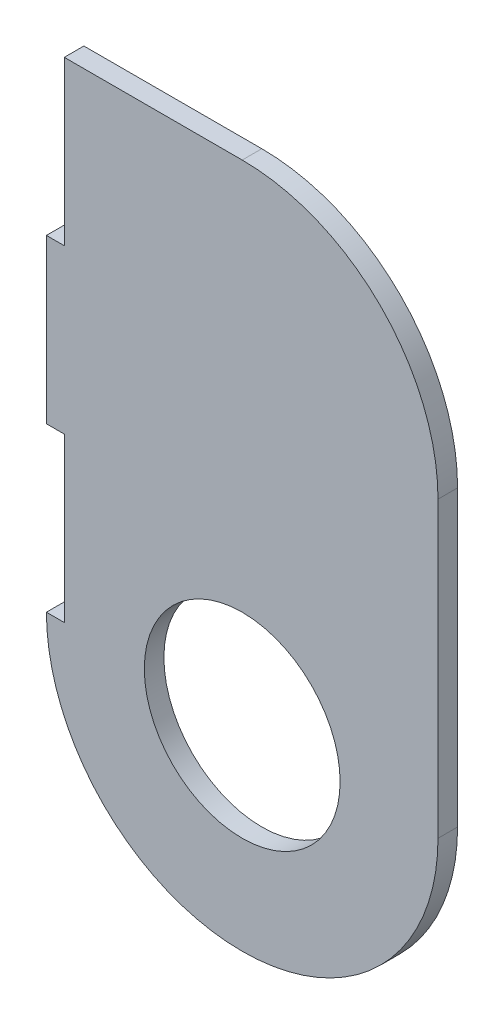
SolidWorks part; units mm, degrees
ref_plane "Plan de face" through (0, 0, 0) normal (0, 0, 1) x (1, 0, 0)
ref_plane "Plan de dessus" through (0, 0, 0) normal (0, 1, 0) x (1, 0, 0)
ref_plane "Plan de droite" through (0, 0, 0) normal (1, 0, 0) x (0, 0, -1)
sketch "Esquisse1" plane through (0, 0, 0) normal (0, 0, 1) x (1, 0, 0)
  line L1 (0, 0) -> (60, 0)
  line L2 (0, 0) -> (0, 105)
  line L3 (0, 105) -> (60, 105)
  line L4 (60, 0) -> (60, 105)
  dimension "D1" = 105
  dimension "D2" = 60
extrude "Boss.-Extru.1" add sketch "Esquisse1" along normal blind 3
fillet "Congé1" radius 30 2 edges at (60, 0, 1.5) (0, 0, 1.5)
sketch "Esquisse2" plane through (0, 0, 3) normal (0, 0, 1) x (1, 0, 0)
  line L0 (30, 0) -> (30, 108.9325) construction
  line L1 (0, 30) -> (60, 30) construction
  circle A0 centre (30, 30) radius 15
  dimension "D1" = 30
  dimension "D2" = 0
extrude "Enlèv. mat.-Extru.1" cut sketch "Esquisse2" against normal blind 3
sketch "Esquisse3" plane through (0, 0, 3) normal (0, 0, 1) x (1, 0, 0)
  line L0 (0, 105) -> (0, 30) construction
  line L1 (0, 30) -> (2.7403, 30)
  line L2 (0, 30) -> (0, 55)
  line L3 (0, 55) -> (2.7403, 55)
  line L4 (2.7403, 30) -> (2.7403, 55)
  line L5 (0, 80) -> (2.7403, 80)
  line L6 (0, 80) -> (0, 105)
  line L7 (0, 105) -> (2.7403, 105)
  line L8 (2.7403, 80) -> (2.7403, 105)
  dimension "D1" = 25
  dimension "D2" = 25
  dimension "D3" = 25
extrude "Enlèv. mat.-Extru.2" cut sketch "Esquisse3" against normal blind 3
fillet "Congé2" radius 30 1 edges at (60, 105, 1.5)
